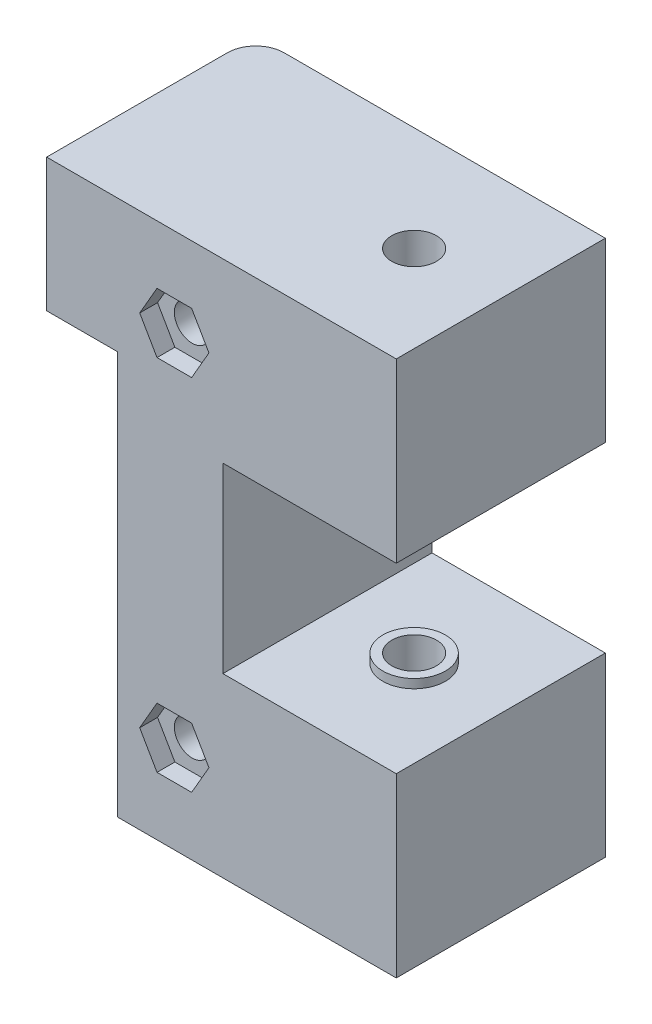
SolidWorks part; units mm, degrees
ref_plane "Front Plane" through (0, 0, 0) normal (0, 0, 1) x (1, 0, 0)
ref_plane "Top Plane" through (0, 0, 0) normal (0, 1, 0) x (1, 0, 0)
ref_plane "Right Plane" through (0, 0, 0) normal (1, 0, 0) x (0, 0, -1)
sketch "MainBlock" plane through (0, 0, 0) normal (0, 0, 1) x (1, 0, 0)
  line L0 (0, 0) -> (39.125, 0)
  line L1 (39.125, 0) -> (39.125, 19.8)
  line L2 (39.125, 19.8) -> (19.725, 19.8)
  line L3 (19.725, 19.8) -> (19.725, 40.2)
  line L4 (19.725, 40.2) -> (39.125, 40.2)
  line L5 (39.125, 40.2) -> (39.125, 60)
  line L6 (39.125, 60) -> (0, 60)
  line L7 (0, 60) -> (0, 0)
  circle A0 centre (14.2875, 50.1) radius 2
  circle A1 centre (14.2875, 9.9) radius 2
  dimension "D4" = 4
  dimension "D1" = 39.125
  dimension "D2" = 60
  dimension "D3" = 20.4
  dimension "D5" = 19.4
  dimension "D6" = 14.2875
  dimension "D7" = 9.9
  dimension "D8" = 9.9
  dimension "D9" = 19.8
  dimension "D10" = 19.8
extrude "MainBlockBoss-Extrude1" add sketch "MainBlock" along normal blind 23.4
sketch "TopHoleCut-Sketch2" plane through (0, 60, 0) normal (0, 1, 0) x (1, 0, 0)
  line L0 (39.125, 0) -> (0, 0) construction
  circle A0 centre (29.425, -11.7) radius 2.5
  dimension "D3" = 5
  dimension "D1" = 11.7
  dimension "D2" = 9.7
extrude "TopHoleCut-Extrude1" cut sketch "TopHoleCut-Sketch2" against normal blind 45
sketch "MountHoleBoreSketch3" plane through (0, 0, 23.4) normal (0, 0, 1) x (1, 0, 0)
  line L1 (18.1625, 50.1) -> (16.225, 53.4558)
  line L2 (16.225, 53.4558) -> (12.35, 53.4558)
  line L3 (12.35, 53.4558) -> (10.4125, 50.1)
  line L4 (10.4125, 50.1) -> (12.35, 46.7442)
  line L5 (12.35, 46.7442) -> (16.225, 46.7442)
  line L6 (16.225, 46.7442) -> (18.1625, 50.1)
  line L7 (18.1625, 9.9) -> (16.225, 13.2558)
  line L8 (16.225, 13.2558) -> (12.35, 13.2558)
  line L9 (12.35, 13.2558) -> (10.4125, 9.9)
  line L10 (10.4125, 9.9) -> (12.35, 6.5442)
  line L11 (12.35, 6.5442) -> (16.225, 6.5442)
  line L12 (16.225, 6.5442) -> (18.1625, 9.9)
  circle A0 centre (14.2875, 50.1) radius 3.3558 construction
  circle A1 centre (14.2875, 9.9) radius 3.3558 construction
  point P10 (14.2875, 53.4558)
  dimension "D1" = 7.75
extrude "MountHoleBoreCut-Extrude2" cut sketch "MountHoleBoreSketch3" against normal blind 2
sketch "TopSpacerSketch4" plane through (0, 40.2, 0) normal (0, -1, 0) x (1, 0, 0)
  circle A0 centre (29.425, 11.7) radius 3.5
  circle A1 centre (29.425, 11.7) radius 2.5
  circle A2 centre (29.425, 11.7) radius 2.5 construction
  dimension "D1" = 7
extrude "TopSpacerBoss-Extrude2" add sketch "TopSpacerSketch4" along normal blind 1
sketch "LowerSpacerSketch5" plane through (0, 19.8, 0) normal (0, 1, 0) x (1, 0, 0)
  circle A0 centre (29.425, -11.7) radius 2.5
  circle A1 centre (29.425, -11.7) radius 2.5 construction
  circle A2 centre (29.425, -11.7) radius 3.5
  circle A3 centre (29.425, -11.7) radius 3.5 construction
extrude "LowerSpacerBoss-Extrude3" add sketch "LowerSpacerSketch5" along normal blind 1
sketch "PushPinHoleSketch1" plane through (0, 0, 0) normal (0, -1, 0) x (1, 0, 0)
  circle A0 centre (29.425, 11.7) radius 1
  circle A1 centre (29.425, 11.7) radius 2.5 construction
  dimension "D1" = 2
extrude "PushPinHoleCut-Extrude1" cut sketch "PushPinHoleSketch1" against normal through all
sketch "MidRailIndentSketch1" plane through (0, 0, 23.4) normal (0, 0, 1) x (1, 0, 0)
  line L0 (0, 60) -> (0, 0) construction
  line L1 (0, 45.1) -> (7.9375, 45.1)
  line L2 (0, 45.1) -> (0, 0)
  line L3 (0, 0) -> (7.9375, 0)
  line L4 (7.9375, 45.1) -> (7.9375, 0)
  line L5 (39.125, 60) -> (0, 60) construction
  line L6 (0, 0) -> (39.125, 0) construction
  dimension "D1" = 14.9
  dimension "D3" = 7.9375
extrude "MidRailIndentCut-Extrude1" cut sketch "MidRailIndentSketch1" against normal through all
fillet "VerticalSupportFillet1" radius 3.175 1 edges at (0, 52.55, 0)
equation "\"BeltTensionerWidth\"= \"MidRailToAlignWithGantryBlock\" + \"BeltTensionerInnerWidth\" / 2 + \"RailThickness\""
equation "\"BeltTensionerHeight\"= 60mm"
equation "\"BeltTensionerDepth\"= \"BeltTensionerBackWallThickness\" + \"BeltTensionerInnerDepth\"'Equals 23.4"
equation "\"BeltTensionerInnerWidth\"= \"20TGT2PulleyDiameter\" + \"BeltTensionerSpaceBetweenPulleyAndWall\""
equation "\"BeltTensionerInnerHeight\"= \"20TGT2PulleyWidth\" * 2 + \"1mmSpacer\" * 3"
equation "\"BeltTensionerBackWallThickness\"= 4mm"
equation "\"BeltTensionerInnerDepth\"= \"20TGT2PulleyDiameter\" + \"BeltTensionerSpaceBetweenPulleyAndWall\""
equation "\"RailThickness\"= .125in'Spec"
equation "\"HoleOffsetFromEdge\"= \"RailThickness\" * 2.5"
equation "\"LinearGBWithRailDepth\"= 12.75mm'Spec"
equation "\"GABDistanceFromBackToFirstPulley\"= 13.5mm"
equation "\"MidRailToAlignWithGantryBlock\"= \"LinearGBWithRailDepth\" + \"GABDistanceFromBackToFirstPulley\"'All outside cogs must align"
equation "\"20TGT2PulleyDiameter\"= 17.9mm'Spec"
equation "\"BeltTensionerSpaceBetweenPulleyAndWall\"= 1.5mm"
equation "\"BeltTensionerMountingHoleDiameter\"= 4.0mm"
equation "\"BeltTensionerMountingHoleOffsetFromTopOrBottom\"= ( \"BeltTensionerHeight\" - \"BeltTensionerInnerHeight\" ) / 4"
equation "\"20TGT2PulleyWidth\"= 8.7mm'The STL of the Pulley in the diagram is a bit larger"
equation "\"1mmSpacer\"= 1mm"
equation "\"SteelShaft5mmHoleDiameter\"= 5mm"
equation "\"BeltTensionerMountingHoleOuterBoreDepth\"= 2mm"
equation "\"BeltTensionerMountingHoleOuterBoreDiameter\"= 7.75mm"
equation "\"7mmx1mmSpacerDiameter\"= 7mm"
equation "\"7mmx1mmSpacerHeight\"= 1mm"
equation "\"D1@MainBlock\" = \"BeltTensionerWidth\""
equation "\"D4@MainBlock\" = \"BeltTensionerMountingHoleDiameter\""
equation "\"D5@MainBlock\" = \"BeltTensionerInnerWidth\""
equation "\"BeltTensionerMountingHoleOffsetFromEdge\"= \"HoleOffsetFromEdge\" + \"RailThickness\" * 2"
equation "\"D6@MainBlock\"=\"BeltTensionerMountingHoleOffsetFromEdge\""
equation "\"D7@MainBlock\"=\"BeltTensionerMountingHoleOffsetFromTopOrBottom\""
equation "\"D8@MainBlock\"=\"BeltTensionerMountingHoleOffsetFromTopOrBottom\""
equation "\"D1@MainBlockBoss-Extrude1\" = \"BeltTensionerDepth\""
equation "\"D1@TopHoleCut-Sketch2\" = \"BeltTensionerDepth\" / 2"
equation "\"D3@TopHoleCut-Sketch2\" = \"SteelShaft5mmHoleDiameter\""
equation "\"D1@MountHoleBoreSketch3\" = \"BeltTensionerMountingHoleOuterBoreDiameter\""
equation "\"D1@MountHoleBoreCut-Extrude2\"=\"BeltTensionerMountingHoleOuterBoreDepth\""
equation "\"D1@TopSpacerSketch4\" = \"7mmx1mmSpacerDiameter\""
equation "\"D1@TopSpacerBoss-Extrude2\" = \"7mmx1mmSpacerHeight\""
equation "\"D1@LowerSpacerBoss-Extrude3\" = \"7mmx1mmSpacerHeight\""
equation "\"SteelPinPushHoleDiameter\"= 2mm"
equation "\"D1@PushPinHoleSketch1\" = \"SteelPinPushHoleDiameter\""
equation "\"BeltTensionerSteelShaftHoleDepthFromTop\"= ( \"SteelShaftLength\" - \"BeltTensionerInnerHeight\" ) / 2 + ( \"BeltTensionerHeight\" - \"BeltTensionerInnerHeight\" ) / 2 + \"BeltTensionerInnerHeight\"'Equals 45"
equation "\"SteelShaftLength\"= 30mm"
equation "\"D1@TopHoleCut-Extrude1\"=\"BeltTensionerSteelShaftHoleDepthFromTop\""
equation "\"D2@TopHoleCut-Sketch2\"=\"BeltTensionerWidth\" -\"MidRailToAlignWithGantryBlock\" - \"RailThickness\""
equation "\"D1@MidRailIndentSketch1\"=\"DistanceAboveMidSideRailToBeltTensioner\""
equation "\"LinearRailWidth\"= 12mm'Spec"
equation "\"MidSideRailVerticalOffset\"= \"LinearRailWidth\" + 3mm'Allows space for RodStabilizer to attach to bottom of MidSideRail"
equation "\"DistanceAboveMidSideRailToBeltTensioner\"= \"VS ToTopOfBeltTensionerAlignedWithYAxisGantryBlockUpperPulley\" - \"V8 ToTopOfMidSideRail\"'Equals 14.9"
equation "\"DistanceFromBeltTensionerTopPulleyToBeltTensionerTop\"= \"7mmx1mmSpacerHeight\" + \"BeltTensionerTopHeight\"'Equals 20.8"
equation "\"BeltTensionerTopHeight\"= ( \"BeltTensionerHeight\" - \"BeltTensionerInnerHeight\" ) / 2'Equals 19.8"
equation "\"GABUpperHeight\"= 4mm"
equation "\"D9@MainBlock\"=\"BeltTensionerTopHeight\""
equation "\"D3@MainBlock\"=\"BeltTensionerInnerHeight\""
equation "\"D2@MainBlock\"=\"BeltTensionerHeight\""
equation "\"LegHeight\"= 70mm'Space needed for PSU/Stepper/Electronics"
equation "\"V1 BottomOfLowerRail\"= \"LegHeight\""
equation "\"LowerEnclosureThickness\"= 5mm"
equation "\"StepperShaftLength\"= 24mm'Pulley will be attached to the end"
equation "\"ZAxisLeadScrewLength\"= 200mm"
equation "\"LM8UUHeight\"= 24mm'Spec"
equation "\"V2 ToBedAtTopOfZAxis\"= \"V1 BottomOfLowerRail\" - \"LowerEnclosureThickness\" + \"StepperShaftLength\" + \"ZAxisLeadScrewLength\" - \"LM8UUHeight\" / 2'Equals 277"
equation "\"BedToBuildPlateStandoffLength\"= 15mm"
equation "\"BuildPlateHeight\"= 8mm'Spec"
equation "\"V4 ToTopOfBuildPlate/HotEndTip\"= \"V2 ToBedAtTopOfZAxis\" + \"BedToBuildPlateStandoffLength\" + \"BuildPlateHeight\""
equation "\"HotEndToTopOfXAxisGB\"= 71.68487mm'Equals 71.68487. Measured after installed onto X-Axis linear rail guide block"
equation "\"LinearGBWidth\"= 27mm'Spec"
equation "\"TopOfGBToBottomOfLinearRail\"= \"LinearGBWidth\" / 2 + \"LinearRailWidth\" / 2'Equals 19.5"
equation "\"V5 ToBottomOfXAxisLinearRail\"= \"V4 ToTopOfBuildPlate/HotEndTip\" + \"HotEndToTopOfXAxisGB\" - \"TopOfGBToBottomOfLinearRail\"'Equals 352.18487"
equation "\"GABMidWallHeight\"= 28mm'Must equal 28 or changes alignment"
equation "\"GABLowerHeight\"= 4mm"
equation "\"GABHeight\"= \"GABLowerHeight\" + \"GABMidWallHeight\" + \"GABUpperHeight\""
equation "\"V6 ToMiddleOfYAxisGantryBlock\"= \"V5 ToBottomOfXAxisLinearRail\" - \"GABHeight\" / 2'Equals 334.18487"
equation "\"V8 ToTopOfMidSideRail\"= \"V6 ToMiddleOfYAxisGantryBlock\" + \"MidSideRailVerticalOffset\"'Equals 349.18487"
equation "\"VS ToTopOfBeltTensionerAlignedWithYAxisGantryBlockUpperPulley\"= \"V5 ToBottomOfXAxisLinearRail\" - \"DistanceFromXAxisLinearRailBottomAndTopOfGantryPulley\" + \"DistanceFromBeltTensionerTopPulleyToBeltTensionerTop\"'Equals 364.08487"
equation "\"DistanceFromXAxisLinearRailBottomAndTopOfGantryPulley\"= \"GABUpperHeight\" + \"GABMidShortRiserHeight\" - \"GABRiserBossOffset\"'Equals 8.9"
equation "\"GABMidShortRiserHeight\"= \"GABMidWallHeight\" / 2 - \"20TGT2PulleyWidth\"'Equals 5.3"
equation "\"GABRiserBossOffset\"= 0.4mm'Aligns Pulleys inside edges to be 2.5mm (.5mm apart top to bottom)"
equation "\"D1@VerticalSupportFillet1\"=\"RailThickness\""
equation "\"D3@MidRailIndentSketch1\"=\"HoleOffsetFromEdge\""
